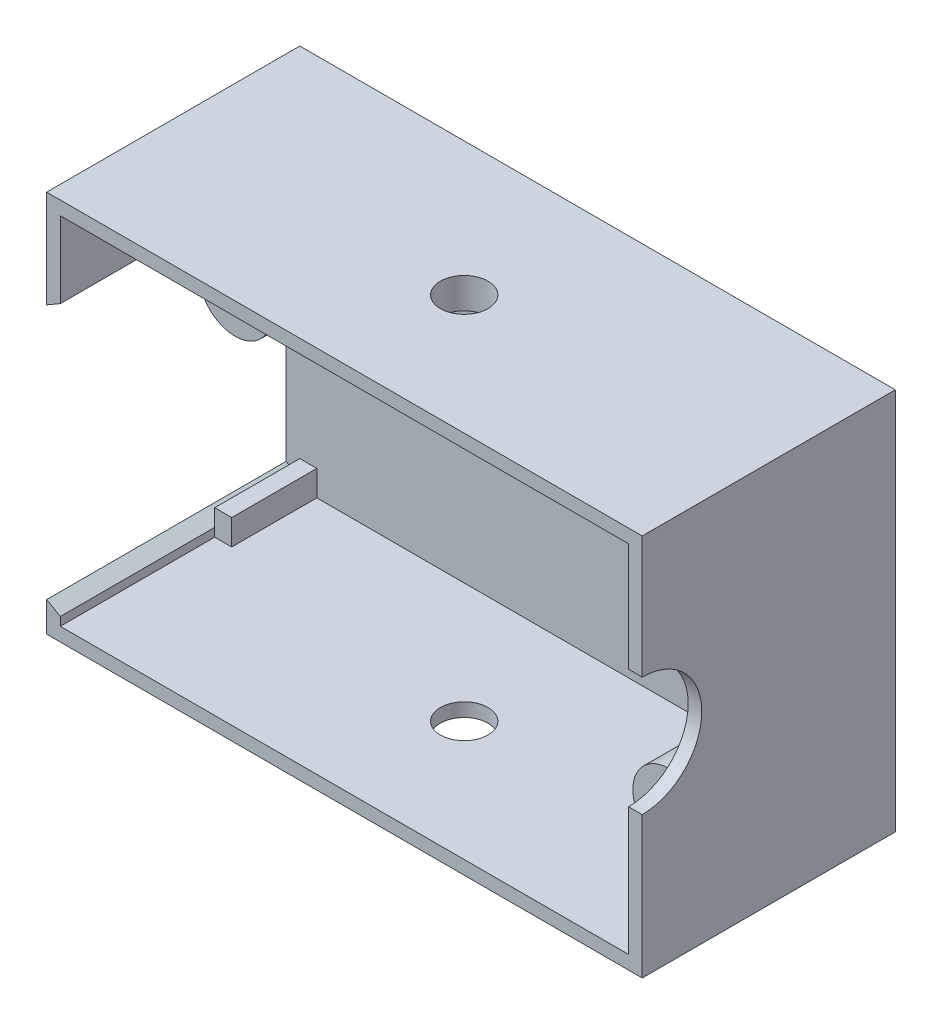
SolidWorks part; units mm, degrees
ref_plane "Front Plane" through (0, 0, 0) normal (0, 0, 1) x (1, 0, 0)
ref_plane "Top Plane" through (0, 0, 0) normal (0, 1, 0) x (1, 0, 0)
ref_plane "Right Plane" through (0, 0, 0) normal (1, 0, 0) x (0, 0, -1)
sketch "Sketch2" plane through (0, 0, 0) normal (0, 0, 1) x (1, 0, 0)
  line L1 (-35, 22.5) -> (35, 22.5)
  line L2 (-35, 22.5) -> (-35, -22.5)
  line L3 (-35, -22.5) -> (35, -22.5)
  line L4 (35, 22.5) -> (35, -22.5)
  line L5 (-35, 22.5) -> (35, -22.5) construction
  line L6 (-35, -22.5) -> (35, 22.5) construction
  point P0 (0, 0)
  dimension "D1" = 70
  dimension "D2" = 45
extrude "Boss-Extrude1" add sketch "Sketch2" along normal blind 1.6
sketch "Sketch3" plane through (0, 0, 1.6) normal (0, 0, 1) x (1, 0, 0)
  line L0 (-35, -22.5) -> (35, -22.5) construction
  line L1 (-22.5, 13.5) -> (28.5, 13.5) construction
  line L2 (-22.5, 13.5) -> (-22.5, -13.5) construction
  line L3 (-22.5, -13.5) -> (28.5, -13.5) construction
  line L4 (28.5, 13.5) -> (28.5, -13.5) construction
  line L6 (35, -22.5) -> (35, 22.5) construction
  circle A0 centre (-22.5, 13.5) radius 3.125
  circle A2 centre (28.5, 13.5) radius 3.125
  circle A3 centre (28.5, -13.5) radius 3.125
  dimension "D1" = 6.25
  dimension "D2" = 9
  dimension "D3" = 6.5
  dimension "D4" = 27
  dimension "D5" = 51
extrude "Cut-Extrude1" cut sketch "Sketch3" against normal blind 1.6
sketch "Sketch4" plane through (0, 0, 1.6) normal (0, 0, 1) x (1, 0, 0)
  line L1 (-33.4, 20.9) -> (33.4, 20.9)
  line L2 (-33.4, 20.9) -> (-33.4, -20.9)
  line L3 (-33.4, -20.9) -> (33.4, -20.9)
  line L4 (35, -22.5) -> (35, 22.5)
  line L5 (35, 22.5) -> (-35, 22.5)
  line L6 (-35, 22.5) -> (-35, -22.5)
  line L7 (-35, -22.5) -> (35, -22.5)
  line L8 (35, -22.5) -> (35, 22.5)
  line L9 (35, 22.5) -> (-35, 22.5)
  line L10 (-35, 22.5) -> (-35, -22.5)
  line L11 (-35, -22.5) -> (35, -22.5)
  line L12 (33.4, 20.9) -> (33.4, -20.9)
  dimension "D2" = 1.6
  dimension "D3" = 1.6
  dimension "D4" = 1.6
  dimension "D5" = 1.6
  dimension "D1" = 0
extrude "Boss-Extrude2" add sketch "Sketch4" along normal blind 28.15
sketch "Sketch5" plane through (0, 0, 1.6) normal (0, 0, 1) x (1, 0, 0)
  circle A1 centre (28.5, -13.5) radius 3.125 construction
  circle A2 centre (28.5, 13.5) radius 3.125 construction
  circle A3 centre (-22.5, 13.5) radius 3.125 construction
  circle A5 centre (28.5, -13.5) radius 3.125
  circle A6 centre (28.5, 13.5) radius 3.125
  circle A7 centre (-22.5, 13.5) radius 3.125
  circle A8 centre (-22.5, 13.5) radius 4.25
  circle A9 centre (28.5, 13.5) radius 4.25
  circle A10 centre (28.5, -13.5) radius 4.25
  dimension "D1" = 8.5
extrude "Boss-Extrude3" add sketch "Sketch5" along normal blind 16.5
sketch "Sketch6" plane through (0, 0, 18.1) normal (0, 0, 1) x (1, 0, 0)
  circle A1 centre (28.5, -13.5) radius 4.25 construction
  circle A2 centre (28.5, 13.5) radius 4.25 construction
  circle A3 centre (-22.5, 13.5) radius 4.25 construction
  circle A5 centre (28.5, -13.5) radius 4.25
  circle A6 centre (28.5, 13.5) radius 4.25
  circle A7 centre (-22.5, 13.5) radius 4.25
  circle A8 centre (-22.5, 13.5) radius 1.75
  circle A9 centre (28.5, 13.5) radius 1.75
  circle A10 centre (28.5, -13.5) radius 1.75
  dimension "D1" = 3.5
extrude "Boss-Extrude4" add sketch "Sketch6" along normal blind 2
chamfer "Chamfer1" distance 1.5 angle 45 3 edges at (30.25, 13.5, 18.1) (30.25, -13.5, 18.1) (-20.75, 13.5, 18.1)
sketch "Sketch7" plane through (35, 0, 0) normal (1, 0, 0) x (0, 0, -1)
  line L0 (-29.75, -22.5) -> (-29.75, 22.5) construction
  line L1 (-29.75, -22.5) -> (0, -22.5) construction
  circle A0 centre (-29.75, 1.13) radius 7
  dimension "D1" = 14
  dimension "D2" = 23.63
extrude "Cut-Extrude2" cut sketch "Sketch7" against normal blind 10
sketch "Sketch8" plane through (0, 0, 29.75) normal (0, 0, 1) x (1, 0, 0)
  line L0 (-35, -18.9762) -> (-33.4, -19.9)
  line L1 (-35, 22.5) -> (-35, -22.5) construction
  line L2 (-33.4, 20.9) -> (-33.4, -20.9) construction
  line L3 (-33.4, -19.9) -> (-33.4, 11.9475)
  line L4 (-33.4, 11.9475) -> (-35, 11.0238)
  line L5 (-35, 11.0238) -> (-35, -18.9762)
  dimension "D1" = 60
  dimension "D2" = 60
  dimension "D3" = 1
  dimension "D4" = 30
extrude "Cut-Extrude3" cut sketch "Sketch8" against normal up to surface (28.15 mm away) up to face at (32.75, 13.5, 1.6)
sketch "Sketch9" plane through (0, 20.9, 0) normal (0, -1, 0) x (1, 0, 0)
  line L0 (33.4, 29.75) -> (-33.4, 1.6) construction
  circle A0 centre (0, 15.675) radius 2.8
  dimension "D1" = 5.6
extrude "Cut-Extrude4" cut sketch "Sketch9" against normal through all both and the other way through all
sketch "Sketch10" plane through (0, 20.9, 0) normal (0, -1, 0) x (1, 0, 0)
  circle A0 centre (0, 15.675) radius 2.8 construction
  circle A1 centre (0, 15.675) radius 2.8
  circle A2 centre (0, 15.675) radius 5
  dimension "D1" = 10
extrude "Boss-Extrude5" add sketch "Sketch10" along normal blind 2
chamfer "Chamfer2" distance 2 angle 45 1 edges at (0, 20.9, 10.675)
sketch "Sketch11" plane through (0, 0, 1.6) normal (0, 0, 1) x (1, 0, 0)
  line L0 (-33.4, 20.9) -> (-33.4, 11.9475) construction
  line L1 (-33.4, -20.9) -> (-31.4, -20.9)
  line L2 (-33.4, -20.9) -> (-33.4, -17.9)
  line L3 (-33.4, -17.9) -> (-31.4, -17.9)
  line L4 (-31.4, -20.9) -> (-31.4, -17.9)
  line L5 (-33.4, 20.9) -> (-31.4, 20.9)
  line L6 (-33.4, 20.9) -> (-33.4, 9.9475)
  line L7 (-33.4, 9.9475) -> (-31.4, 9.9475)
  line L8 (-31.4, 20.9) -> (-31.4, 9.9475)
  line L9 (33.4, 20.9) -> (-33.4, 20.9) construction
  point P11 (0, 0)
  point P14 (-33.4, 20.8124)
  dimension "D1" = 2
  dimension "D2" = 2
  dimension "D3" = 2
extrude "Boss-Extrude6" add sketch "Sketch11" along normal blind 10
equation "\"D1\"= 1.6"
